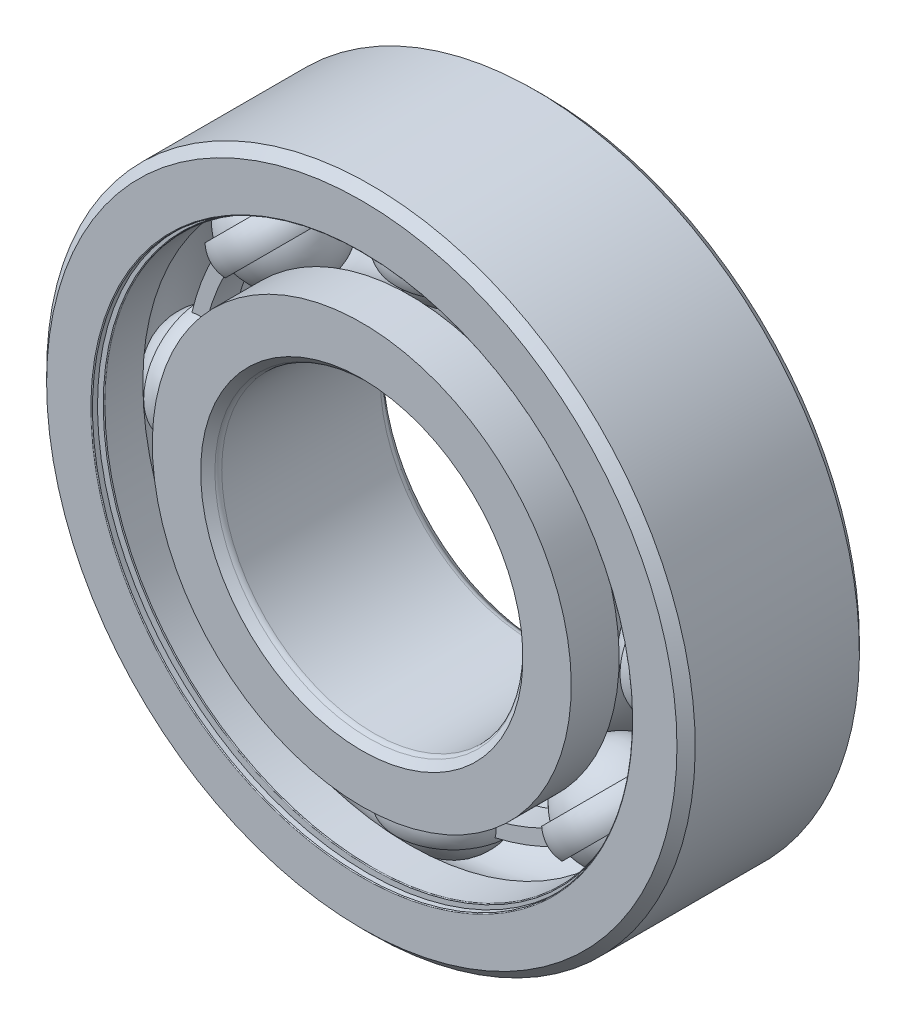
SolidWorks part; units mm, degrees
ref_plane "Front Plane" through (0, 0, 0) normal (0, 0, 1) x (1, 0, 0)
ref_plane "Top Plane" through (0, 0, 0) normal (0, 1, 0) x (1, 0, 0)
ref_plane "Right Plane" through (0, 0, 0) normal (1, 0, 0) x (0, 0, -1)
sketch "Sketch1" plane through (0, 0, 0) normal (0, 0, 1) x (1, 0, 0)
  line L0 (-16, 0) -> (16, 0) construction
  line L1 (-7.5, 0) -> (7.5, 0) construction
  circle A0 centre (0, 0) radius 7.5 construction
  circle A1 centre (0, 0) radius 16 construction
  point P3 (0, 0)
  point P6 (0, 0)
  point P7 (0, -7.5)
  point P11 (0, -16)
  point P12 (0, 7.5)
  point P13 (0, 16)
  dimension "OD" = 32
  dimension "ID" = 15
sketch "Sketch2" plane through (0, 0, 0) normal (1, 0, 0) x (0, 0, -1)
  line L0 (-4.5, 16) -> (4.5, 16) construction
  line L1 (0, 16) -> (0, -16) construction
  line L2 (4.05, 16) -> (-4.05, 16)
  line L3 (-4.05, 16) -> (-4.5, 15.55)
  line L4 (-4.5, 15.55) -> (-4.5, 13.1654)
  line L5 (-4.5, 13.1654) -> (-2.1375, 13.1654)
  line L6 (4.5, 13.1654) -> (2.1375, 13.1654)
  line L7 (4.5, 15.55) -> (4.5, 13.1654)
  line L8 (4.05, 16) -> (4.5, 15.55)
  line L9 (0, 16) -> (0, 11.75) construction
  line L10 (0, 11.75) -> (0, 7.5) construction
  line L11 (0, 16) -> (0, -16) construction
  line L12 (-4.5, 0) -> (4.5, 0) construction
  line L13 (4.5, 7.5) -> (-4.5, 7.5) construction
  line L14 (0, 14.3136) -> (0, 9.1864) construction
  line L15 (-4.5, -7.5) -> (4.5, -7.5) construction
  line L16 (-4.5, -7.5) -> (-4.5, 7.5) construction
  line L17 (4.5, 16) -> (4.5, -16) construction
  arc A0 (-2.1375, 13.1654) -> (2.1375, 13.1654) centre (0, 11.75) cw
  circle A1 centre (0, 11.75) radius 2.5636 construction
  point P14 (0, 7.5)
  point P17 (0, 0)
  point P21 (0, 16)
  point P29 (0, 7.5)
  point P30 (0, -7.5)
  point P35 (0, 14.3136)
  dimension "Approx. Ball Dia." = 5.1273
  dimension "Width" = 9
  dimension "D1" = 45
  dimension "D2" = 0.45
  dimension "D3" = 4.275
  dimension "D4" = 1.4154
  dimension "For Shaft Diameter" = 15
  dimension "For Housing ID" = 32
sketch "Sketch3" plane through (0, 0, 0) normal (1, 0, 0) x (0, 0, -1)
  line L0 (4.05, 16) -> (4.5, 15.55) construction
  line L1 (4.5, 15.55) -> (4.5, 13.1654) construction
  line L2 (4.5, 13.1654) -> (2.1375, 13.1654) construction
  line L3 (-4.5, 13.1654) -> (-2.1375, 13.1654) construction
  line L4 (-4.5, 15.55) -> (-4.5, 13.1654) construction
  line L5 (-4.05, 16) -> (-4.5, 15.55) construction
  line L6 (4.05, 16) -> (-4.05, 16) construction
  line L7 (4.05, 16) -> (4.5, 15.55)
  line L8 (4.5, 15.55) -> (4.5, 13.1654)
  line L9 (4.5, 13.1654) -> (2.1375, 13.1654)
  line L10 (-4.5, 13.1654) -> (-2.1375, 13.1654)
  line L11 (-4.5, 15.55) -> (-4.5, 13.1654)
  line L12 (-4.05, 16) -> (-4.5, 15.55)
  line L13 (4.05, 16) -> (-4.05, 16)
  arc A0 (2.1375, 13.1654) -> (-2.1375, 13.1654) centre (0, 11.75) ccw construction
  arc A1 (2.1375, 13.1654) -> (-2.1375, 13.1654) centre (0, 11.75) ccw
revolve "Revolve1" add sketch "Sketch3" angle 360 about L12
sketch "Sketch8" plane through (0, 0, 0) normal (1, 0, 0) x (0, 0, -1)
  line L0 (-4.5, 13.1654) -> (-2.1375, 13.1654) construction
  line L1 (-4.212, 13.1654) -> (-4.05, 13.1654)
  line L2 (-4.212, 13.1654) -> (-4.212, 14.1103) construction
  line L3 (-4.212, 14.1103) -> (-4.05, 14.1103)
  line L4 (-4.05, 13.1654) -> (-4.05, 14.1103)
  line L5 (4.5, 13.1654) -> (2.1375, 13.1654) construction
  line L6 (4.05, 13.1654) -> (4.212, 13.1654)
  line L7 (4.05, 13.1654) -> (4.05, 14.1103)
  line L8 (4.05, 14.1103) -> (4.212, 14.1103)
  line L9 (4.212, 13.1654) -> (4.212, 14.1103) construction
  line L10 (-4.05, 14.1103) -> (4.05, 14.1103) construction
  line L11 (0, 16) -> (0, -16) construction
  line L12 (-4.212, 14.1103) -> (-4.212, 15.0551) construction
  line L13 (-4.212, 15.0551) -> (-4.212, 16) construction
  line L14 (-4.5, 16) -> (4.5, 16) construction
  line L15 (-4.212, 13.1654) -> (-4.5, 13.1654)
  line L16 (-4.5, 13.1654) -> (-4.5, 13.3274)
  line L17 (-4.5, 15.55) -> (-4.5, 13.1654) construction
  line L18 (-4.5, 13.3274) -> (-4.212, 13.3274)
  line L19 (-4.212, 13.3274) -> (-4.212, 14.1103)
  line L20 (4.212, 13.1654) -> (4.5, 13.1654)
  line L21 (4.5, 13.1654) -> (4.5, 13.3274)
  line L22 (4.5, 15.55) -> (4.5, 13.1654) construction
  line L23 (4.5, 13.3274) -> (4.212, 13.3274)
  line L24 (4.212, 13.3274) -> (4.212, 14.1103)
  point P12 (0, 14.1103)
  dimension "D1" = 8.1
  dimension "D2" = 0.162
revolve "Cut-Revolve1" cut sketch "Sketch8" angle 360 about L12
sketch "Sketch4" plane through (0, 0, 0) normal (1, 0, 0) x (0, 0, -1)
  line L0 (0, 16) -> (0, -16) construction
  line L1 (0, 16) -> (0, -16) construction
  line L2 (-4.05, 7.5) -> (-4.5, 7.95)
  line L3 (-4.5, 7.95) -> (-4.5, 10.3346)
  line L5 (-4.5, 10.3346) -> (-2.1375, 10.3346)
  line L6 (-4.05, 7.5) -> (4.05, 7.5)
  line L8 (4.05, 7.5) -> (4.5, 7.95)
  line L10 (4.5, 7.95) -> (4.5, 10.3346)
  line L11 (4.5, 10.3346) -> (2.1375, 10.3346)
  line L12 (-4.5, 15.55) -> (-4.5, 13.1654) construction
  line L13 (4.05, 16) -> (4.5, 15.55) construction
  line L15 (4.5, -15.55) -> (4.5, 15.55) construction
  line L16 (4.05, 16) -> (4.05, -16) construction
  arc A1 (2.1375, 10.3346) -> (-2.1375, 10.3346) centre (0, 11.75) cw
  circle A2 centre (0, 11.75) radius 2.5636 construction
  point P1 (0, 7.5)
revolve "Revolve2" add sketch "Sketch4" angle 360 about L12
sketch "Sketch5" plane through (0, 0, 0) normal (1, 0, 0) x (0, 0, -1)
  line L0 (-2.5636, 11.75) -> (2.5636, 11.75)
  arc A2 (-2.5636, 11.75) -> (2.5636, 11.75) centre (0, 11.75) cw
  arc A3 (2.1375, 13.1654) -> (-2.1375, 13.1654) centre (0, 11.75) ccw construction
revolve "Revolve3" add sketch "Sketch5" angle 360 about L0
sketch "Sketch6" plane through (0, 0, 0) normal (1, 0, 0) x (0, 0, -1)
  line L0 (-2.1375, 13.1654) -> (-2.1375, 12.4577) construction
  line L1 (-2.1375, 12.4577) -> (-2.1375, 11.75) construction
  line L2 (-2.1375, 11.75) -> (-2.1375, 11.0423) construction
  line L3 (-2.1375, 11.0423) -> (-2.1375, 10.3346) construction
  line L4 (-4.5, 12.4577) -> (-4.1607, 12.4577) construction
  line L5 (-2.1375, 12.4577) -> (-2.1375, 11.0423) construction
  line L7 (-4.1607, 12.4577) -> (-3.8213, 12.4577) construction
  line L8 (-3.8213, 12.4577) -> (-3.482, 12.4577) construction
  line L10 (0, 16) -> (0, -16) construction
  line L11 (0, 16) -> (0, -16) construction
  line L12 (-4.5, 13.1654) -> (-4.5, 12.4577) construction
  line L13 (-2.8033, 12.4577) -> (-2.464, 12.4577) construction
  line L14 (-4.5, 15.55) -> (-4.5, -15.55) construction
  line L15 (-4.5, 12.4577) -> (-4.5, 11.75) construction
  line L16 (-4.5, 11.75) -> (-4.5, 11.0423) construction
  line L17 (-4.5, 11.0423) -> (-4.5, 10.3346) construction
  line L18 (-3.482, 12.4577) -> (-3.1427, 12.4577) construction
  line L19 (-3.1427, 12.4577) -> (-2.8033, 12.4577) construction
  line L20 (-2.464, 12.4577) -> (-2.8033, 12.4577)
  line L21 (-4.5, 11.0423) -> (-4.1607, 11.0423) construction
  line L22 (-4.1607, 11.0423) -> (-3.8213, 11.0423) construction
  line L23 (-3.8213, 11.0423) -> (-3.482, 11.0423) construction
  line L24 (-3.482, 11.0423) -> (-3.1427, 11.0423) construction
  line L25 (-3.1427, 11.0423) -> (-2.8033, 11.0423) construction
  line L26 (-2.8033, 11.0423) -> (-2.464, 11.0423) construction
  line L27 (-2.464, 11.0423) -> (-2.8033, 11.0423)
  line L28 (-3.1427, 12.4577) -> (-3.1427, 11.0423) construction
  line L30 (-2.973, 12.4577) -> (-2.973, 11.0423) construction
  circle A0 centre (0, 11.75) radius 2.5636 construction
  arc A2 (-2.8033, 11.0423) -> (-2.8033, 12.4577) centre (-1.4122, 11.75) cw
  arc A3 (-2.464, 12.4577) -> (-2.464, 11.0423) centre (0, 11.75) ccw
revolve "Revolve4" add sketch "Sketch6" angle 360 about L11
sketch "Sketch7" plane through (0, 0, 0) normal (0, 0, 1) x (1, 0, 0)
  line L0 (-2.5636, 11.75) -> (2.5636, 11.75) construction
  line L1 (0, 9.1864) -> (0, 14.3136) construction
  line L2 (0, 0) -> (4.4965, 10.8556) construction
  line L8 (0, 16) -> (0, -16) construction
  line L9 (8.3085, 8.3085) -> (8.8089, 8.8089)
  line L10 (0, 16) -> (0, -16) construction
  line L11 (0, 12.4577) -> (0, 11.75)
  arc A1 (8.3085, 8.3085) -> (0, 11.75) centre (0, 0) ccw
  arc A2 (8.8089, 8.8089) -> (0, 12.4577) centre (0, 0) ccw
  dimension "D1" = 45
  dimension "D2" = 5.1273
extrude "Boss-Extrude1" add sketch "Sketch7" along normal mid plane 1.5
pattern_circular "CirPattern1" count 8 over 360 about axis through (0, 0, 4.5) along (0, 0, -1) of bodies 104 134
pattern_circular "CirPattern2" count 8 over 360 about axis through (0, 0, 4.5) along (0, 0, -1) of "Revolve4", "Boss-Extrude1" reverse direction yes
fillet "Fillet1" radius 0.0405 4 edges at (0, -13.1654, -4.05) (0, -13.3274, -4.5) (0, -13.1654, 4.05) (0, -13.3274, 4.5)
fillet "Fillet2" radius 0.3375 2 edges at (0, -7.5, -4.05) (0, -7.5, 4.05)
ref_plane "Plane1" through (4.4965, 10.8556, 0) normal (0.3827, 0.9239, 0) x (0.9239, -0.3827, 0)
sketch "Sketch9" plane through (4.4965, 10.8556, 0) normal (0.3827, 0.9239, 0) x (0.9239, -0.3827, 0)
  line L0 (-2.128, -0.75) -> (-2.128, -2.25)
  line L1 (-2.128, -2.25) -> (-0.9231, -2.25)
  line L2 (-0.9231, -2.25) -> (0, -1.4755)
  line L3 (0, -1.4755) -> (0.9231, -2.25)
  line L4 (0.9231, -2.25) -> (2.128, -2.25)
  line L5 (2.128, -2.25) -> (2.128, -0.75)
  line L6 (2.128, -0.75) -> (-2.128, -0.75)
  line L7 (0, -0.75) -> (0, 0) construction
  line L8 (-2.128, -0.75) -> (-2.128, 0) construction
  dimension "D1" = 1.5
  dimension "D2" = 0.75
  dimension "D3" = 40
extrude "Boss-Extrude2" [suppressed] add sketch "Sketch9" along normal blind 2.2432 draft 15 and the other way blind 2.2432 draft 10 separate body draft outward yes other way draft outward yes
fillet "Fillet3" [suppressed] radius 0.45
mirror "Mirror1" [suppressed] about plane through (0, 0, 0) normal (0, 0, 1) of bodies 149
pattern_circular "CirPattern3" [suppressed] count 8 over 360 about axis through (0, 0, 4.5) along (0, 0, -1) of bodies 158 149
equation "\"D2@Sketch2\" = \"Width@Sketch2\" * .05"
equation "\"D3@Sketch2\"=\"Width@Sketch2\" * .475"
equation "\"D4@Sketch2\" =  (  (  ( \"OD@Sketch1\" - \"Width@Sketch2\" )  / 2 )  / 3.25 )  / 2.5"
equation "\"D1@Boss-Extrude1\" = \"Width@Sketch2\" / 6"
equation "\"D1@Sketch8\"=\"Width@Sketch2\"*.9"
equation "\"D2@Sketch8\"=\"D1@Sketch8\"*.02"
equation "\"D1@Fillet1\" = \"D2@Sketch8\" * .25"
equation "\"D1@Fillet2\" = \"D2@Sketch2\" * .75"
equation "\"Approx No of Balls@CirPattern1\" = ( pi * \"OD@Sketch1\" ) * .4 / \"Approx. Ball Dia.@Sketch2\""
equation "\"D1@Sketch7\" = 360 / \"Approx No of Balls@CirPattern1\""
equation "\"D1@CirPattern2\" = \"Approx No of Balls@CirPattern1\""
equation "\"D2@Sketch7\"=\"Approx. Ball Dia.@Sketch2\""
equation "\"D2@Sketch9\" = \"D1@Boss-Extrude1\" * .5"
equation "\"D1@Sketch9\"=\"D2@Sketch9\"*2"
equation "\"D1@Boss-Extrude2\"=\"Approx. Ball Dia.@Sketch2\"*.4375"
equation "\"D2@Boss-Extrude2\"=\"D1@Boss-Extrude2\""
equation "\"D1@CirPattern3\" = \"Approx No of Balls@CirPattern1\""
equation "\"D1@Fillet3\"=\"D1@Sketch9\" * .3"
